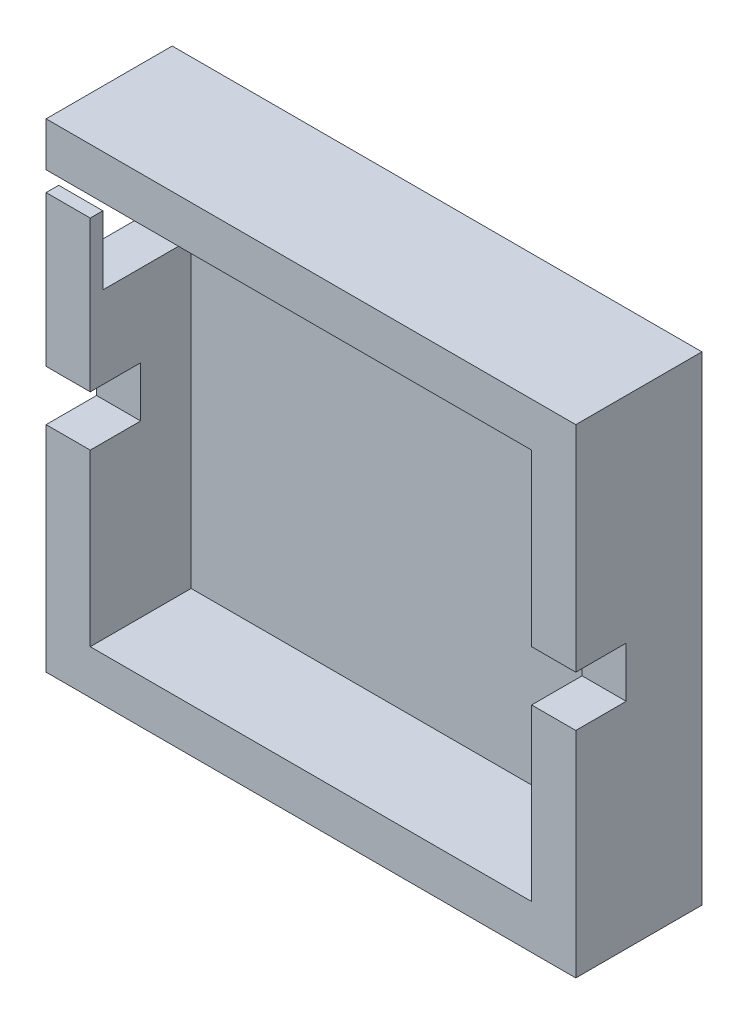
SolidWorks part; units mm, degrees
ref_plane "前视基准面" through (0, 0, 0) normal (0, 0, 1) x (1, 0, 0)
ref_plane "上视基准面" through (0, 0, 0) normal (0, 1, 0) x (1, 0, 0)
ref_plane "右视基准面" through (0, 0, 0) normal (1, 0, 0) x (0, 0, -1)
sketch "草图1" plane through (0, 0, 0) normal (0, 0, 1) x (1, 0, 0)
  line L1 (0, 0) -> (35, 0) construction
  line L2 (0, 0) -> (0, 31) construction
  line L3 (0, 31) -> (35, 31) construction
  line L4 (35, 0) -> (35, 31) construction
  line L5 (0, 0) -> (-3.5, 0) construction
  line L6 (0, 0) -> (0, -3.5) construction
  line L7 (0, -3.5) -> (-3.5, -3.5) construction
  line L8 (-3.5, 0) -> (-3.5, -3.5) construction
  line L9 (-3.5, -3.5) -> (38.5, -3.5)
  line L10 (-3.5, -3.5) -> (-3.5, 34.5)
  line L11 (-3.5, 34.5) -> (38.5, 34.5)
  line L12 (38.5, -3.5) -> (38.5, 34.5)
  dimension "D1" = 35
  dimension "D2" = 31
  dimension "D3" = 3.5
  dimension "D4" = 3.5
  dimension "D5" = 38
  dimension "D6" = 42
extrude "凸台-拉伸1" add sketch "草图1" along normal blind 2
sketch "草图2" plane through (0, 0, 2) normal (0, 0, 1) x (1, 0, 0)
  line L1 (0, 0) -> (35, 0)
  line L2 (0, 0) -> (0, 31)
  line L3 (0, 31) -> (35, 31)
  line L4 (35, 0) -> (35, 31)
  line L5 (-3.5, -3.5) -> (38.5, -3.5)
  line L6 (-3.5, -3.5) -> (-3.5, 34.5)
  line L7 (-3.5, 34.5) -> (38.5, 34.5)
  line L8 (38.5, -3.5) -> (38.5, 34.5)
  dimension "D1" = 31
  dimension "D2" = 35
  dimension "D3" = 42
  dimension "D4" = 38
extrude "凸台-拉伸2" add sketch "草图2" along normal blind 8
sketch "草图3" plane through (-3.5, 0, 0) normal (-1, 0, 0) x (0, 0, 1)
  line L0 (10, 34.5) -> (10, -3.5) construction
  line L1 (0, 34.5) -> (2, 34.5)
  line L2 (0, 34.5) -> (0, 31)
  line L3 (0, 31) -> (2, 31)
  line L4 (2, 34.5) -> (2, 31)
  line L5 (2, 31) -> (9, 31)
  line L6 (2, 31) -> (2, 24)
  line L7 (2, 24) -> (9, 24)
  line L8 (9, 31) -> (9, 24)
  line L9 (9, 31) -> (10, 31)
  line L10 (9, 31) -> (9, 29.4354)
  line L11 (9, 29.4354) -> (10, 29.4354)
  line L12 (10, 31) -> (10, 29.4354)
  line M6 (10, -3.5) -> (10, 34.5)
  dimension "D1" = 2
  dimension "D2" = 3.5
  dimension "D3" = 7
extrude "切除-拉伸1" cut sketch "草图3" against normal blind 6.5 contours L6 L7 L5 M6 | L10 L9 L12 L11 region at (-3.5, 27.5, 5.5)
sketch "草图6" plane through (0, 0, 10) normal (0, 0, 1) x (1, 0, 0)
  line L0 (-3.5, 34.5) -> (-3.5, -3.5) construction
  line L1 (35, 15.5) -> (35, 17.5)
  line L2 (0, 31) -> (0, 0) construction
  line L3 (0, 15.5) -> (0, 17.5)
  line L4 (0, 17.5) -> (-3.5, 17.5)
  line L5 (0, 17.5) -> (0, 13.5)
  line L6 (0, 13.5) -> (-3.5, 13.5)
  line L7 (-3.5, 17.5) -> (-3.5, 13.5)
  line L8 (35, 0) -> (35, 31) construction
  line L9 (38.5, -3.5) -> (38.5, 34.5) construction
  line L10 (35, 17.5) -> (38.5, 17.5)
  line L11 (35, 17.5) -> (35, 13.5)
  line L12 (35, 13.5) -> (38.5, 13.5)
  line L13 (38.5, 17.5) -> (38.5, 13.5)
  line M9 (35, 31) -> (35, 0)
  line M11 (0, 0) -> (0, 31)
  line M15 (-3.5, 34.5) -> (-3.5, -3.5)
  line M17 (38.5, -3.5) -> (38.5, 34.5)
  dimension "D1" = 4
  dimension "D2" = 2
extrude "切除-拉伸3" cut sketch "草图6" against normal blind 4 contours L6 L4 M11 M15 | L12 L10 M9 M17 region at (36.75, 15.5, 10) region at (-1.75, 15.5, 10)
sketch "草图7" plane through (0, 0, 0) normal (0, 0, -1) x (-1, 0, 0)
  line L0 (-5, 34.5) -> (-5, 23.9)
  line L1 (-38.5, 34.5) -> (3.5, 34.5) construction
  line L2 (-28, 34.5) -> (-28, 28.1)
  line L3 (-28, 28.1) -> (-38.5, 28.1)
  line L4 (-38.5, -3.5) -> (-38.5, 34.5) construction
  line L5 (-5, 23.9) -> (3.5, 23.9)
  line L6 (3.5, 34.5) -> (3.5, -3.5) construction
  line L8 (-28, 28.1) -> (-5, 28.1)
  line L9 (-28, 28.1) -> (-28, 23.9)
  line L10 (-28, 23.9) -> (-5, 23.9)
  line L11 (-5, 28.1) -> (-5, 23.9)
  dimension "D1" = 10.6
  dimension "D2" = 6.4
  dimension "D3" = 10.5
  dimension "D4" = 8.5
extrude "切除-拉伸4" cut sketch "草图7" against normal blind 10 contours L9 L10 L0 L8 region at (16.5, 26, 0)
